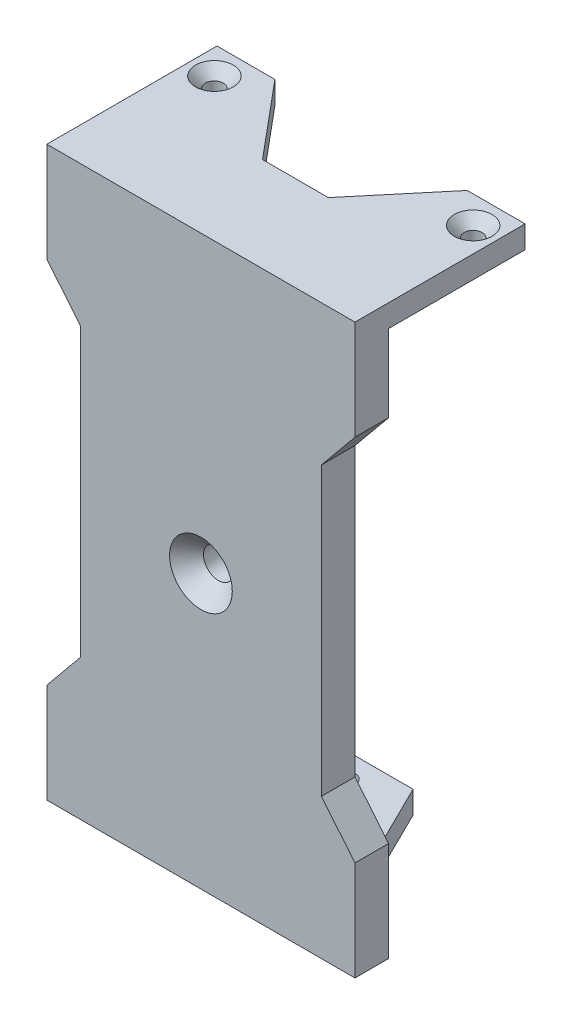
SolidWorks part; units mm, degrees
ref_plane "Front Plane" through (0, 0, 0) normal (0, 0, 1) x (1, 0, 0)
ref_plane "Top Plane" through (0, 0, 0) normal (0, 1, 0) x (1, 0, 0)
ref_plane "Right Plane" through (0, 0, 0) normal (1, 0, 0) x (0, 0, -1)
sketch "Sketch1" plane through (0, 0, 0) normal (0, 0, 1) x (1, 0, 0)
  line L0 (0, 0) -> (55, 0) construction
  line L1 (55, 0) -> (55, -93.4) construction
  line L2 (55, -93.4) -> (0, -93.4) construction
  line L3 (0, -93.4) -> (0, 0) construction
  line L7 (55, 0) -> (0, 0)
  line L8 (55, -46.7) -> (0, -46.7) construction
  line L10 (27.5, 0) -> (27.5, -102.43) construction
  line L11 (55, 0) -> (55, -13.7874)
  line L12 (55, -13.7874) -> (49, -21.0837)
  line L13 (49, -21.0837) -> (49, -72.3163)
  line L14 (55, -79.6126) -> (49, -72.3163)
  line L15 (55, -93.4) -> (55, -79.6126)
  line L16 (55, -93.4) -> (0, -93.4)
  line L17 (0, -93.4) -> (0, -79.6126)
  line L18 (0, -79.6126) -> (6, -72.3163)
  line L19 (6, -21.0837) -> (6, -72.3163)
  line L20 (0, -13.7874) -> (6, -21.0837)
  line L21 (0, 0) -> (0, -13.7874)
  circle A1 centre (48, -6) radius 4.5 construction
  point P14 (49, -46.7)
  point P16 (27.5, -93.4)
  point P24 (27.5, -93.4)
  dimension "D4" = 9
  dimension "D1" = 55
  dimension "D2" = 93.4
  dimension "D3" = 6
  dimension "D5" = 7
  dimension "D6" = 6
extrude "Boss-Extrude1" add sketch "Sketch1" along normal blind 6 contours L19 L18 L17 L16 L15 L14 L13 L12 L11 L7 L21 L20
sketch "Sketch2" plane through (0, 0, 0) normal (0, 1, 0) x (1, 0, 0)
  line L0 (0, -6) -> (0, 0)
  line L1 (0, 0) -> (0, 24.3682)
  line L2 (27.5, -6) -> (27.5, 12.073) construction
  line L3 (55, -6) -> (0, -6) construction
  line L4 (0, 24.3682) -> (10.336, 24.3682)
  line L5 (10.336, 24.3682) -> (21.6251, 10.8693)
  line L6 (21.6251, 10.8693) -> (33.3749, 10.8693)
  line L7 (55, 0) -> (55, 24.3682)
  line L8 (55, 24.3682) -> (44.664, 24.3682)
  line L9 (44.664, 24.3682) -> (33.3749, 10.8693)
  line L10 (0, -6) -> (55, -6)
  line L11 (55, -6) -> (55, 0)
  point P16 (27.5, 10.8693)
extrude "Boss-Extrude2" add sketch "Sketch2" along normal blind 4
sketch "Sketch3" plane through (0, -93.4, 0) normal (0, -1, 0) x (1, 0, 0)
  line L0 (55, 6) -> (0, 6)
  line L1 (0, 6) -> (0, 0)
  line L2 (0, 0) -> (7.9746, 0)
  line L3 (55, 0) -> (0, 0) construction
  line L4 (7.9746, 0) -> (20, -24.3649)
  line L5 (27.5, 6) -> (27.5, -18.9998) construction
  line L6 (20, -24.3649) -> (35, -24.3649)
  line L7 (55, 6) -> (55, 0)
  line L8 (55, 0) -> (47.0254, 0)
  line L9 (47.0254, 0) -> (35, -24.3649)
  line L10 (55, 0) -> (0, 0) construction
  point P16 (27.5, -24.3649)
  dimension "D1" = 15
extrude "Boss-Extrude3" add sketch "Sketch3" along normal blind 4
sketch "Sketch4" plane through (0, 0, 6) normal (0, 0, 1) x (1, 0, 0)
  line L0 (0, 4) -> (55, 4) construction
  line L1 (0, 4) -> (0, -13.7874) construction
  circle A0 centre (27.5, -48.6) radius 2.7
  dimension "D1" = 5.4
  dimension "D2" = 52.6
  dimension "D3" = 27.5
extrude "Cut-Extrude1" cut sketch "Sketch4" against normal up to surface (6 mm away) up to face at (27.5, -59.375, 0)
ref_plane "Plane1" through (0, 0, 2.85) normal (0, 0, 1) x (1, 0, 0)
sketch "Sketch5" plane through (0, 0, 2.85) normal (0, 0, 1) x (1, 0, 0)
  circle A0 centre (27.5, -48.6) radius 2.7 construction
  circle A1 centre (27.5, -48.6) radius 2.7
sketch "Sketch6" plane through (0, 0, 6) normal (0, 0, 1) x (1, 0, 0)
  circle A0 centre (27.5, -48.6) radius 5.6
  dimension "D1" = 11.2
loft "Cut-Loft1" cut profiles "Sketch6", "Sketch5" connector at (23.0345, -45.2208, 6) connector at (25.1786, -47.2212, 2.85)
sketch "Sketch7" plane through (0, 4, 0) normal (0, 1, 0) x (1, 0, 0)
  line L0 (27.5, -6) -> (27.5, 28.4444) construction
  line L1 (0, -6) -> (55, -6) construction
  line L3 (55, -6) -> (55, 24.3682) construction
  circle A0 centre (50.6, 19.5) radius 1.6
  circle A1 centre (4.4, 19.5) radius 1.6
  dimension "D1" = 3.2
  dimension "D2" = 4.4
  dimension "D3" = 25.5
extrude "Cut-Extrude2" cut sketch "Sketch7" against normal up to surface (4 mm away) up to face at (27.5, 0, -14.9015)
sketch "Sketch8" plane through (0, -97.4, 0) normal (0, -1, 0) x (1, 0, 0)
  line L0 (55, 6) -> (0, 6) construction
  circle A0 centre (27.5, -20) radius 1.6
  point P5 (27.5, 6)
  dimension "D1" = 3.2
  dimension "D2" = 26
extrude "Cut-Extrude3" cut sketch "Sketch8" against normal up to surface (4 mm away) up to face at (27.5, -93.4, -12.1825)
ref_plane "Plane2" through (0, -95.5, 0) normal (0, -1, 0) x (-1, 0, 0)
sketch "Sketch9" plane through (0, -95.5, 0) normal (0, -1, 0) x (-1, 0, 0)
  circle A0 centre (-27.5, 20) radius 1.6 construction
  circle A1 centre (-27.5, 20) radius 1.6
sketch "Sketch10" plane through (0, -97.4, 0) normal (0, -1, 0) x (1, 0, 0)
  circle A0 centre (27.5, -20) radius 3.375
  dimension "D1" = 6.75
loft "Cut-Loft2" cut profiles "Sketch10", "Sketch9" connector at (28.1449, -97.4, -16.6872) connector at (26.6572, -95.5, -21.36)
ref_plane "Plane3" through (0, 2.1, 0) normal (0, 1, 0) x (1, 0, 0)
sketch "Sketch11" plane through (0, 2.1, 0) normal (0, 1, 0) x (1, 0, 0)
  circle A0 centre (50.6, 19.5) radius 1.6 construction
  circle A1 centre (50.6, 19.5) radius 1.6
sketch "Sketch12" plane through (0, 4, 0) normal (0, 1, 0) x (1, 0, 0)
  circle A0 centre (50.6, 19.5) radius 3.375
  point P5 (0, 0)
  point P7 (0, 0)
  dimension "D2" = 6.75
loft "Cut-Loft3" cut profiles "Sketch12", "Sketch11" connector at (50.3139, 4, -22.8629) connector at (50.1018, 2.1, -21.0204)
pattern_linear "LPattern1" count 2 spacing 46.2 along (-1, 0, 0) of "Cut-Loft3"
